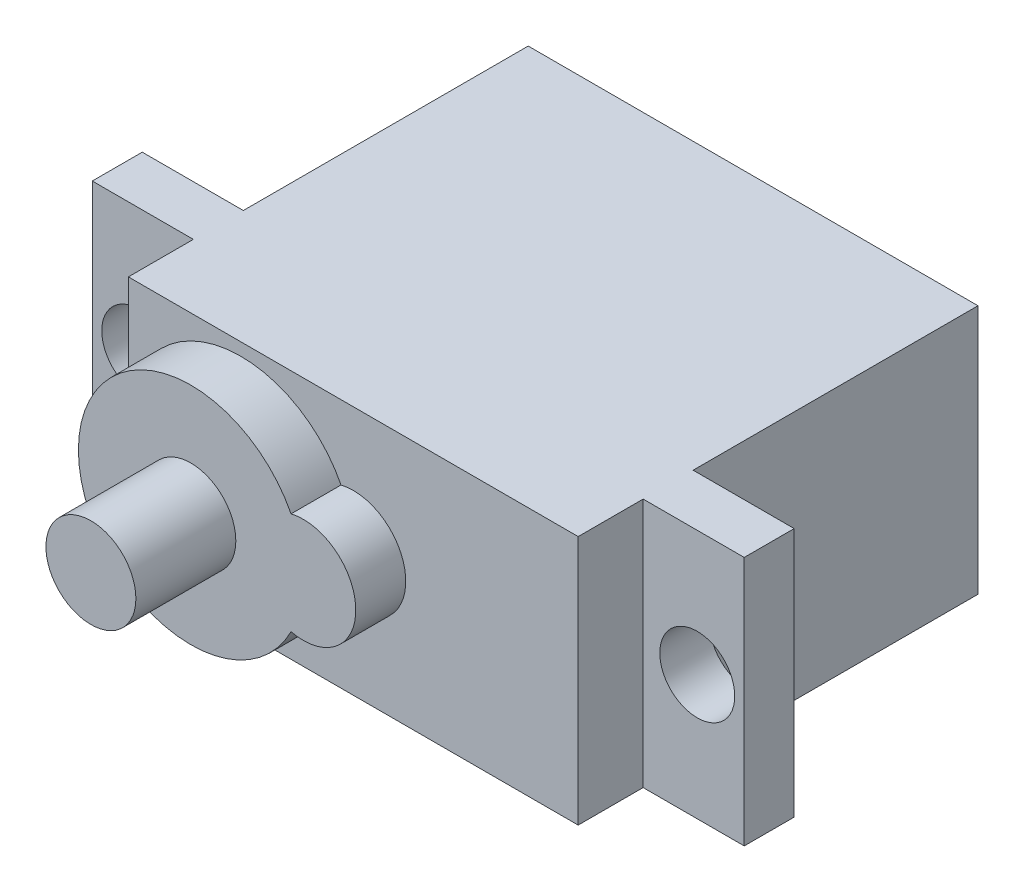
SolidWorks part; units mm, degrees
ref_plane "Front Plane" through (0, 0, 0) normal (0, 0, 1) x (1, 0, 0)
ref_plane "Top Plane" through (0, 0, 0) normal (0, 1, 0) x (1, 0, 0)
ref_plane "Right Plane" through (0, 0, 0) normal (1, 0, 0) x (0, 0, -1)
sketch "Sketch2" plane through (0, 0, 0) normal (0, 0, 1) x (1, 0, 0)
  line L0 (-81.3007, 67.2823) -> (-81.3007, 54.5823) construction
  line L1 (-92.7307, 67.2823) -> (-69.8707, 67.2823)
  line L2 (-92.7307, 67.2823) -> (-92.7307, 54.5823)
  line L3 (-92.7307, 54.5823) -> (-69.8707, 54.5823)
  line L4 (-69.8707, 67.2823) -> (-69.8707, 54.5823)
  line L5 (-92.7307, 67.2823) -> (-97.8677, 67.2823)
  line L6 (-92.7307, 67.2823) -> (-92.7307, 54.5823)
  line L7 (-92.7307, 54.5823) -> (-97.8677, 54.5823)
  line L8 (-97.8677, 67.2823) -> (-97.8677, 54.5823)
  line L9 (-69.8707, 54.5823) -> (-64.7338, 54.5823)
  line L10 (-64.7338, 67.2823) -> (-64.7338, 54.5823)
  line L11 (-69.8707, 67.2823) -> (-64.7338, 67.2823)
  line L12 (-69.8707, 67.2823) -> (-69.8707, 54.5823)
  circle A0 centre (-95.4807, 60.9323) radius 1.905
  circle A1 centre (-67.1207, 60.9323) radius 1.905
  dimension "D1" = 22.86
  dimension "D2" = 5.1369
extrude "Boss-Extrude1" add sketch "Sketch2" along normal blind 3.302 and the other way blind 17.018 contours L1 L0 L3 L4 | L0 L1 L2 L3 region at (-75.5857, 60.9323, 0) region at (-87.0157, 60.9323, 0)
extrude "Boss-Extrude2" add sketch "Sketch2<5>" against normal blind 2.54 contours L11 L4 L9 L10 A1 | L5 L8 L7 L2 A0 region at (-92.8677, 60.9323, 0) region at (-67.3023, 67.1453, 0)
sketch "Sketch2<5>" plane through (0, 0, 0) normal (0, 0, 1) x (1, 0, 0) same geometry as "Sketch2"
sketch "Sketch3" plane through (0, 0, 3.302) normal (0, 0, 1) x (1, 0, 0)
  line L0 (-95.4807, 60.9323) -> (-67.1207, 60.9323) construction
  line L1 (-92.7307, 67.2823) -> (-92.7307, 54.5823) construction
  line L2 (-81.3007, 67.2823) -> (-81.3007, 54.5823) construction
  line L3 (-81.3007, 54.5823) -> (-81.3007, 67.2823) construction
  line L4 (-92.7307, 54.5823) -> (-69.8707, 54.5823) construction
  line L5 (-92.7307, 67.2823) -> (-69.8707, 67.2823) construction
  arc A0 (-81.923, 63.5257) -> (-81.923, 58.339) centre (-87.0157, 60.9323) ccw
  arc A1 (-81.923, 58.339) -> (-81.923, 63.5257) centre (-81.3007, 60.9323) ccw
  dimension "D1" = 11.43
  dimension "D2" = 5.334
extrude "Boss-Extrude3" add sketch "Sketch3" along normal blind 2.54
sketch "Sketch4" plane through (0, 0, 5.842) normal (0, 0, 1) x (1, 0, 0)
  circle A0 centre (-87.0157, 60.9323) radius 2.286
  dimension "D1" = 4.572
extrude "Boss-Extrude4" add sketch "Sketch4" along normal blind 5.08
